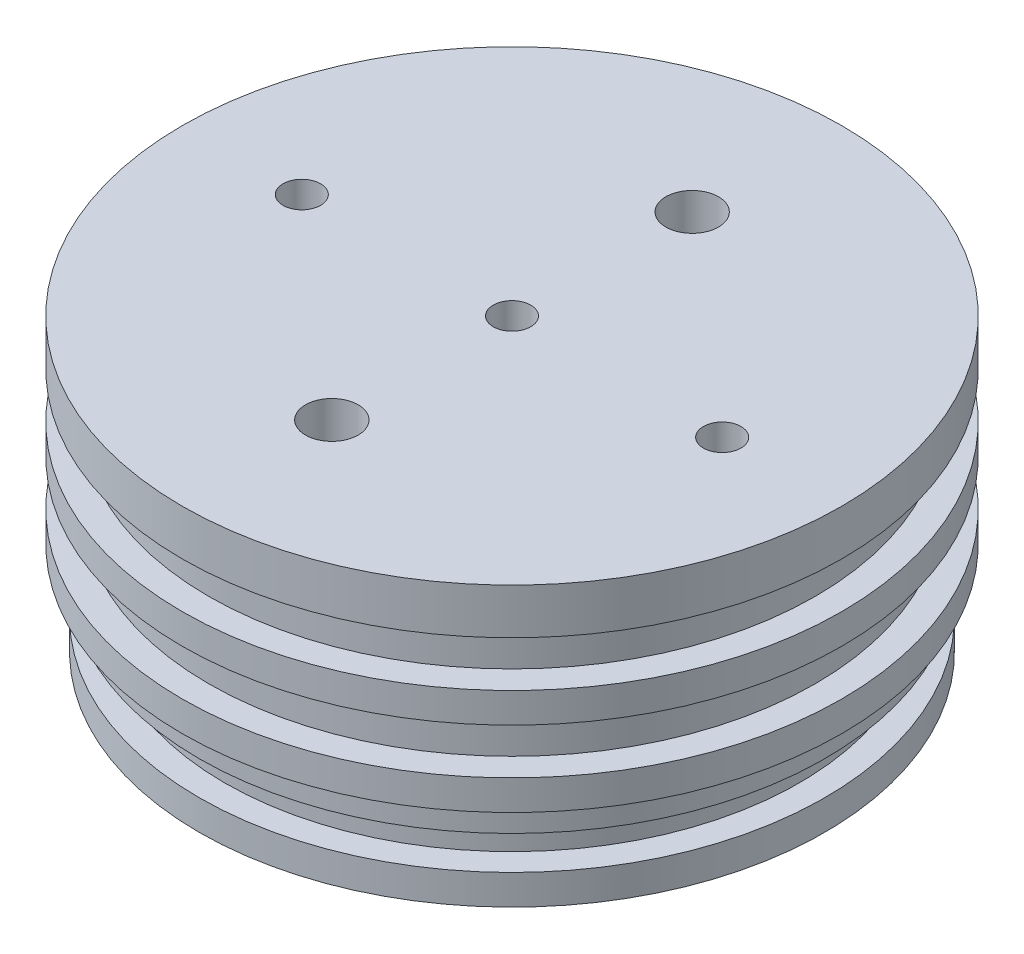
SolidWorks part; units mm, degrees
material "6061-T6 (SS)"
ref_plane "Front Plane" through (0, 0, 0) normal (0, 0, 1) x (1, 0, 0)
ref_plane "Top Plane" through (0, 0, 0) normal (0, 1, 0) x (1, 0, 0)
ref_plane "Right Plane" through (0, 0, 0) normal (1, 0, 0) x (0, 0, -1)
sketch "Sketch1" plane through (0, 0, 0) normal (0, 1, 0) x (1, 0, 0)
  circle A0 centre (0, 0) radius 69.723
  dimension "D1" = 139.446
extrude "Boss-Extrude1" add sketch "Sketch1" along normal blind 41.656
ref_plane "Plane1" through (69.723, 0, 0) normal (1, 0, 0) x (0, 0, -1)
sketch "Sketch3" plane through (0, 0, 0) normal (1, 0, 0) x (0, 0, -1)
  line L0 (69.723, 0) -> (69.723, 41.656) construction
  line L1 (69.723, 32.004) -> (64.135, 32.004)
  line L2 (69.723, 32.004) -> (69.723, 22.352)
  line L3 (69.723, 22.352) -> (64.135, 22.352)
  line L4 (64.135, 32.004) -> (64.135, 22.352)
  line L5 (-69.723, 0) -> (69.723, 0) construction
  line L6 (69.723, 16.002) -> (64.135, 16.002)
  line L7 (69.723, 16.002) -> (69.723, 6.35)
  line L8 (69.723, 6.35) -> (64.135, 6.35)
  line L9 (64.135, 16.002) -> (64.135, 6.35)
  dimension "D1" = 9.652
  dimension "D2" = 9.652
  dimension "D3" = 64.135
  dimension "D4" = 64.135
  dimension "D5" = 6.35
  dimension "D6" = 6.35
ref_axis "Axis1" through (0, 41.656, 0) along (0, -1, 0)
revolve "Cut-Revolve1" cut sketch "Sketch3" angle 360 about axis through (0, 41.656, 0) along (0, -1, 0)
sketch "Sketch4" plane through (0, 0, 0) normal (0, -1, 0) x (1, 0, 0)
  circle A0 centre (0, 0) radius 66.167
  dimension "D1" = 132.334
extrude "Boss-Extrude2" add sketch "Sketch4" along normal blind 19.8374
sketch "Sketch5" plane through (0, 0, 0) normal (1, 0, 0) x (0, 0, -1)
  line L0 (66.167, -19.8374) -> (66.167, 0) construction
  line L1 (66.167, -13.4874) -> (60.7695, -13.4874)
  line L2 (66.167, -13.4874) -> (66.167, -6.35)
  line L3 (66.167, -6.35) -> (60.7695, -6.35)
  line L4 (60.7695, -13.4874) -> (60.7695, -6.35)
  line L6 (-66.167, -19.8374) -> (66.167, -19.8374) construction
  dimension "D1" = 60.7695
  dimension "D2" = 7.1374
  dimension "D3" = 6.35
revolve "Cut-Revolve2" cut sketch "Sketch5" angle 360 about axis through (0, 41.656, 0) along (0, -1, 0)
sketch "Sketch7" plane through (0, -19.8374, 0) normal (0, -1, 0) x (1, 0, 0)
  circle A0 centre (0, 0) radius 24.765
  dimension "D1" = 49.53
extrude "Cut-Extrude1" [suppressed] cut sketch "Sketch7" against normal blind 38.1 contours A0
sketch "Sketch8" plane through (0, 41.656, 0) normal (0, 1, 0) x (1, 0, 0)
  line L0 (0, 0) -> (0, 38.1) construction
  line L1 (0, -33.8214) -> (0, 33.8214) construction
  dimension "D1" = 38.1
hole_wizard "Pipe Tap Drill for 1/4 Tap1" positions "3DSketch1" profile "Sketch9" hole size "1/4" standard "ANSI Inch" end condition up to next
sketch3d "3DSketch1"
  point P0 (0, 41.656, -38.1)
sketch "Sketch9" plane through (0, 41.656, -38.1) normal (1, 0, 0) x (0, 0, 1)
  line L0 (0, 0) -> (0, 61.4934)
  line L1 (0, 61.4934) -> (5.5626, 61.4934)
  line L2 (5.5626, 61.4934) -> (5.5626, 0)
  line L5 (5.5626, 0) -> (0, 0)
  line L11 (0, -6.35) -> (0, 107.95) construction
  dimension "Thru Hole Dia." = 11.1252
  dimension "Thru Hole Depth" = 61.4934
mirror "Mirror1" about plane through (0, 0, 0) normal (0, 0, 1) of "Pipe Tap Drill for 1/4 Tap1"
sketch "Sketch13" plane through (0, 41.656, 0) normal (0, 1, 0) x (1, 0, 0)
  point P0 (0, 0)
hole_wizard "Tap Drill for 3/8-16 Tap1" positions "3DSketch4" profile "Sketch16" hole size "3/8-16" standard "ANSI Inch"
sketch3d "3DSketch4"
  point P0 (0, 41.656, 0)
sketch "Sketch16" plane through (0, 41.656, 0) normal (1, 0, 0) x (0, 0, 1)
  line L0 (0, 0) -> (0, 27.7847)
  line L1 (0, 27.7847) -> (3.9687, 25.4)
  line L2 (3.9687, 25.4) -> (3.9687, 0)
  line L5 (3.9687, 0) -> (0, 0)
  line L10 (0, 27.7847) -> (-3.9688, 25.4) construction
  line L11 (0, -6.35) -> (0, 107.95) construction
  dimension "Hole Dia." = 7.9375
  dimension "Hole Depth" = 25.4
  dimension "Drill Angle" = 118
sketch "Sketch21" plane through (0, 41.656, 0) normal (0, 1, 0) x (1, 0, 0)
  point P0 (0, 38.1)
  point P1 (0, -38.1)
hole_wizard "Pipe Tap Drill for 1/4 Tap2" positions "3DSketch9" profile "Sketch23" hole size "1/4" standard "ANSI Inch" end condition up to next
sketch3d "3DSketch9"
  point P0 (0, 41.656, 38.1)
  point P3 (0, 41.656, -38.1)
sketch "Sketch23" plane through (0, 41.656, 38.1) normal (1, 0, 0) x (0, 0, 1)
  line L0 (0, 0) -> (0, 61.4934)
  line L1 (0, 61.4934) -> (5.5626, 61.4934)
  line L2 (5.5626, 61.4934) -> (5.5626, 0)
  line L5 (5.5626, 0) -> (0, 0)
  line L11 (0, -6.35) -> (0, 107.95) construction
  dimension "Thru Hole Dia." = 11.1252
  dimension "Thru Hole Depth" = 61.4934
sketch "snap ring groove" [suppressed] plane through (0, 0, 0) normal (0, 0, 1) x (1, 0, 0)
  line L2 (-66.167, -19.8374) -> (66.167, -19.8374) construction
  line L3 (-24.765, -16.6624) -> (-26.9494, -16.6624)
  line L4 (-24.765, -16.6624) -> (-24.765, -14.8844)
  line L5 (-24.765, -14.8844) -> (-26.9494, -14.8844)
  line L6 (-26.9494, -16.6624) -> (-26.9494, -14.8844)
  line L7 (-24.765, 18.2626) -> (-24.765, -19.8374) construction
  point P9 (-26.9494, -15.7734)
  dimension "D1" = 1.778
  dimension "D2" = 26.9494
  dimension "D3" = 3.175
revolve "Cut-Revolve3" [suppressed] cut sketch "snap ring groove" angle 360 about axis through (0, 41.656, 0) along (0, -1, 0)
sketch "Sketch24" plane through (0, 41.656, 0) normal (0, 1, 0) x (1, 0, 0)
  line L0 (-33.8214, 0) -> (33.8214, 0) construction
  point P0 (-44.45, 0)
  point P1 (44.45, 0)
  dimension "D1" = 44.45
  dimension "D2" = 44.45
hole_wizard "Tap Drill for 3/8-16 Tap2" positions "3DSketch11" profile "Sketch26" hole size "3/8-16" standard "ANSI Inch"
sketch3d "3DSketch11"
  point P0 (-44.45, 41.656, 0)
  point P3 (44.45, 41.656, 0)
sketch "Sketch26" plane through (-44.45, 41.656, 0) normal (1, 0, 0) x (0, 0, 1)
  line L0 (0, 0) -> (0, 21.4347)
  line L1 (0, 21.4347) -> (3.9687, 19.05)
  line L2 (3.9687, 19.05) -> (3.9687, 0)
  line L5 (3.9687, 0) -> (0, 0)
  line L10 (0, 21.4347) -> (-3.9688, 19.05) construction
  line L11 (0, -6.35) -> (0, 107.95) construction
  dimension "Hole Dia." = 7.9375
  dimension "Hole Depth" = 19.05
  dimension "Drill Angle" = 118
